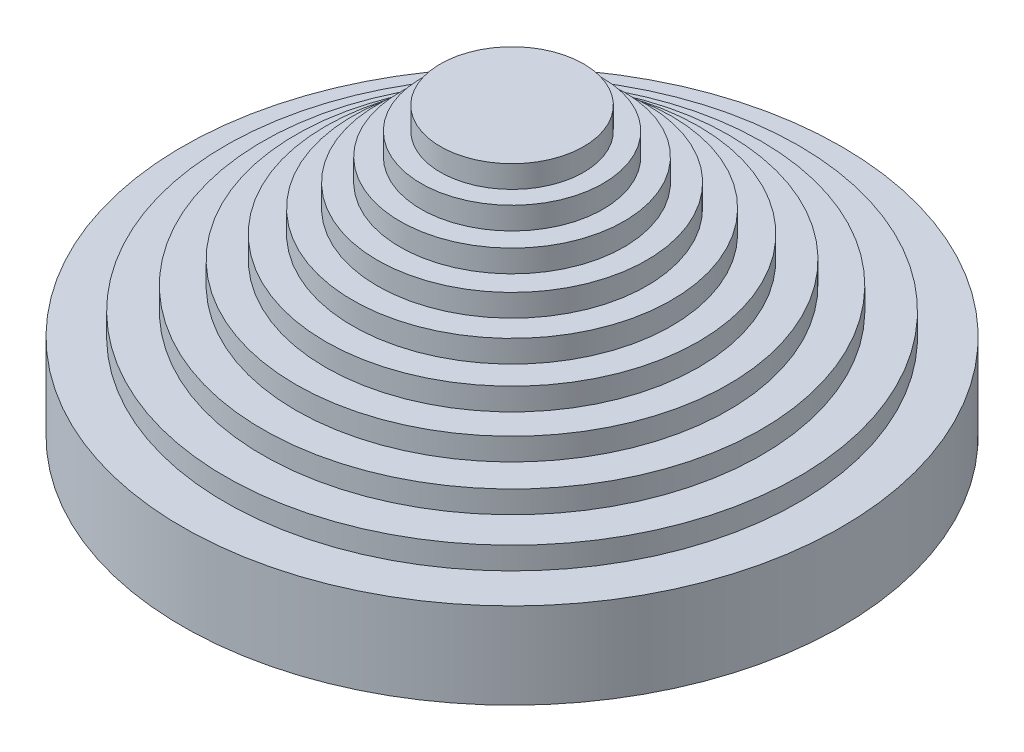
SolidWorks part; units mm, degrees
ref_plane "Front Plane" through (0, 0, 0) normal (0, 0, 1) x (1, 0, 0)
ref_plane "Top Plane" through (0, 0, 0) normal (0, 1, 0) x (1, 0, 0)
ref_plane "Right Plane" through (0, 0, 0) normal (1, 0, 0) x (0, 0, -1)
sketch "Sketch1" plane through (0, 0, 0) normal (1, 0, 0) x (0, 0, -1)
  line L0 (-11.5, 0) -> (-11.5, 3)
  line L1 (-11.5, 3) -> (-10.0043, 3)
  line L2 (-10.0043, 3) -> (-10.0043, 3.7778)
  line L3 (-10.0043, 3.7778) -> (-8.7033, 3.7778)
  line L4 (-8.7033, 3.7778) -> (-8.7033, 4.5556)
  line L5 (-8.7033, 4.5556) -> (-7.5484, 4.5556)
  line L6 (-7.5484, 4.5556) -> (-7.5484, 5.3333)
  line L7 (-7.5484, 5.3333) -> (-6.5092, 5.3333)
  line L8 (-6.5092, 5.3333) -> (-6.5092, 6.1111)
  line L9 (-6.5092, 6.1111) -> (-5.5653, 6.1111)
  line L10 (-5.5653, 6.1111) -> (-5.5653, 6.8889)
  line L11 (-5.5653, 6.8889) -> (-4.702, 6.8889)
  line L12 (-4.702, 6.8889) -> (-4.702, 7.6667)
  line L13 (-4.702, 7.6667) -> (-3.9087, 7.6667)
  line L14 (-3.9087, 7.6667) -> (-3.9087, 8.4444)
  line L15 (-3.9087, 8.4444) -> (-3.1768, 8.4444)
  line L16 (-3.1768, 8.4444) -> (-3.1768, 9.2222)
  line L17 (-3.1768, 9.2222) -> (-2.5, 9.2222)
  line L18 (-2.5, 9.2222) -> (-2.5, 10)
  line L19 (-2.5, 10) -> (0, 10)
  line L20 (0, 0) -> (0, 13.1925) construction
  line L21 (-11.5, 0) -> (0, 0)
  line L22 (0, 10) -> (0, 0)
  arc A0 (-2.5, 10) -> (-11.5, 3) centre (-23.2027, 27.332) cw construction
  dimension "D7" = 27
  dimension "D1" = 23
  dimension "D4" = 3
  dimension "D5" = 10
  dimension "D6" = 5
revolve "Revolve1" add sketch "Sketch1" angle 360 about L20
sketch "Sketch2" plane through (0, 0, 0) normal (0, -1, 0) x (1, 0, 0)
  line L0 (-1.4491, 1.45) -> (1.4491, 1.45)
  circle A0 centre (0, 0) radius 3.2
  arc A1 (-1.4491, 1.45) -> (1.4491, 1.45) centre (0, 0) ccw
  dimension "D1" = 6.4
  dimension "D2" = 4.1
  dimension "D3" = 1.45
extrude "Boss-Extrude1" add sketch "Sketch2" along normal blind 2.6 contours A0
extrude "Cut-Extrude1" cut sketch "Sketch2<3>" along normal blind 3 and the other way blind 3 contours A1 L0
sketch "Sketch2<3>" plane through (0, 0, 0) normal (0, -1, 0) x (1, 0, 0) same geometry as "Sketch2"
